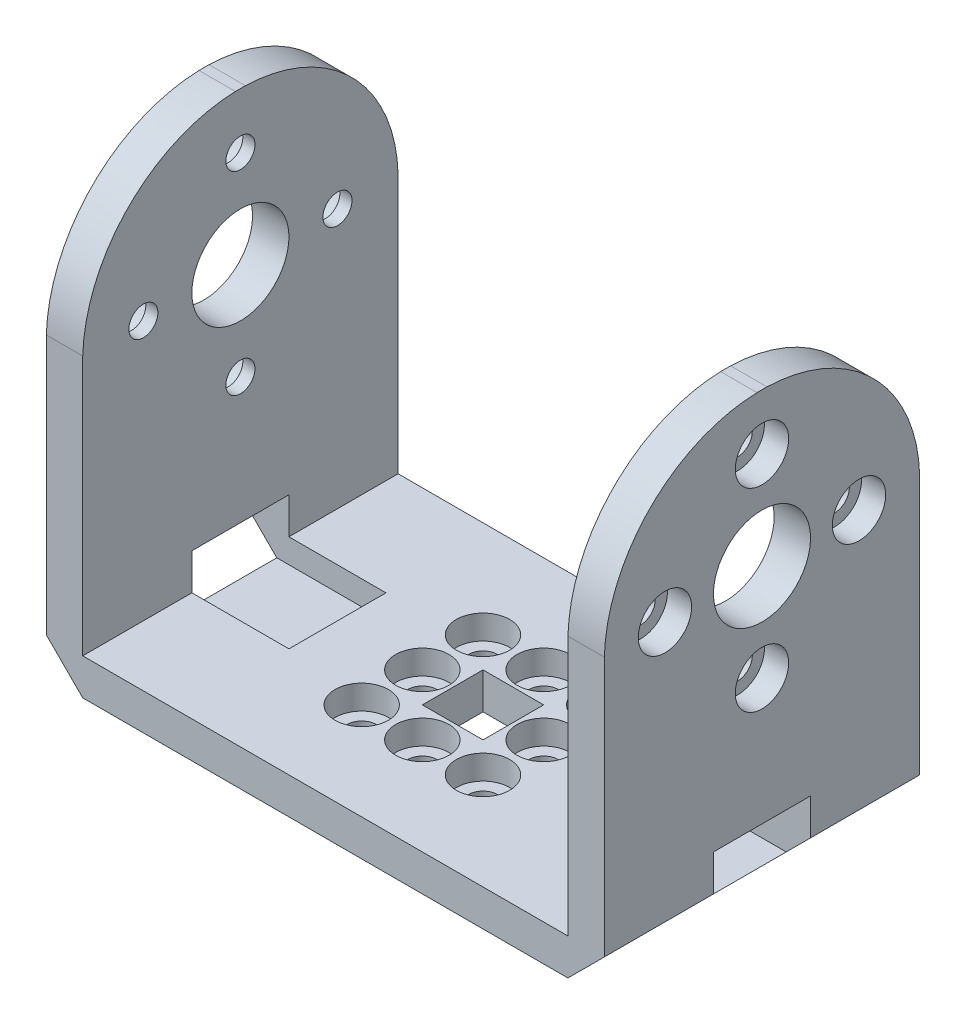
SolidWorks part; units mm, degrees
ref_plane "Front" through (0, 0, 0) normal (0, 0, 1) x (1, 0, 0)
ref_plane "Top" through (0, 0, 0) normal (0, 1, 0) x (1, 0, 0)
ref_plane "Right" through (0, 0, 0) normal (1, 0, 0) x (0, 0, -1)
sketch "草图1" plane through (0, 0, 0) normal (0, 1, 0) x (1, 0, 0)
  line L1 (-23, 13) -> (23, 13)
  line L2 (-23, 13) -> (-23, -13)
  line L3 (-23, -13) -> (23, -13)
  line L4 (23, 13) -> (23, -13)
  line L5 (-23, 13) -> (23, -13) construction
  line L6 (-23, -13) -> (23, 13) construction
  point P0 (0, 0)
  dimension "D1" = 46
  dimension "D2" = 26
extrude "凸台-拉伸1" add sketch "草图1" along normal blind 3
sketch "草图2" plane through (0, 3, 0) normal (0, 1, 0) x (1, 0, 0)
  line L0 (-23, -13) -> (23, -13) construction
  line L1 (-23, 13) -> (-20, 13)
  line L2 (-23, 13) -> (-23, -13)
  line L3 (-23, -13) -> (-20, -13)
  line L4 (-20, 13) -> (-20, -13)
  line L6 (23, 13) -> (20, 13)
  line L7 (23, 13) -> (23, -13)
  line L8 (23, -13) -> (20, -13)
  line L9 (20, 13) -> (20, -13)
extrude "凸台-拉伸2" add sketch "草图2" along normal blind 34
sketch "草图3" plane through (-23, 0, 0) normal (-1, 0, 0) x (0, 0, 1)
  line L0 (-13, 37) -> (-13, 0) construction
  line L1 (13, 37) -> (13, 0) construction
  arc A1 (-13, 23.5872) -> (13, 24.4128) centre (0, 24) cw
extrude "切除-拉伸1" cut sketch "草图3" against normal through all and the other way through all body kept at (-23, 0, -13)
sketch "草图4" plane through (-23, 0, 0) normal (-1, 0, 0) x (0, 0, 1)
  line L0 (-13, 24.4128) -> (13, 24.4128) construction
  line L1 (0, 37) -> (0, 0) construction
  line L2 (-0.4128, 37) -> (0.4128, 37) construction
  line L3 (-13, 0) -> (13, 0) construction
  circle A1 centre (0, 24.4128) radius 4
extrude "切除-拉伸2" cut sketch "草图4" against normal through all
sketch "草图7" plane through (-23, 0, 0) normal (-1, 0, 0) x (0, 0, 1)
  line L0 (-13, 24.4128) -> (13, 24.4128) construction
  line L1 (0, 37) -> (0, 10.3049) construction
  line L2 (-0.4128, 37) -> (0.4128, 37) construction
  point P4 (8, 24.4128)
  point P5 (0, 24.4128)
  point P11 (0, 32.4128)
  point P12 (-8, 24.4128)
  point P13 (0, 16.4128)
  dimension "D1" = 8
  dimension "D2" = 8
  dimension "D3" = 8
  dimension "D4" = 8
hole_wizard "M2 凹头盖螺钉的柱形沉头孔2" positions "3D草图2" profile "草图8" counterbore size "M2" standard "ANSI Metric" end condition up to next
sketch3d "3D草图2"
  point P0 (-23, 32.4128, 0)
  point P3 (-23, 24.4128, -8)
  point P6 (-23, 24.4128, 8)
  point P9 (-23, 16.4128, 0)
sketch "草图8" plane through (-23, 32.4128, 0) normal (0, 1, 0) x (0, 0, 1)
  line L0 (0, 0) -> (0, 46)
  line L1 (0, 46) -> (1.2, 46)
  line L3 (1.2, 46) -> (1.2, 2)
  line L4 (1.2, 2) -> (2.2, 2)
  line L5 (2.2, 2) -> (2.2, 0)
  line L7 (2.2, 0) -> (0, 0)
  line L11 (0, -6.35) -> (0, 107.95) construction
  dimension "通孔孔直径" = 2.4
  dimension "通孔孔深度" = 46
  dimension "柱形沉头孔直径" = 4.4
  dimension "柱形沉头孔深度" = 2
mirror "镜向2" about plane through (0, 0, 0) normal (1, 0, 0) of "M2 凹头盖螺钉的柱形沉头孔2"
chamfer "倒角1" distance 3 angle 45 2 edges at (23, 0, 0) (-23, 0, 0)
sketch "草图15" plane through (23, 0, 0) normal (1, 0, 0) x (0, 0, -1)
  line L0 (-13, 3) -> (13, 3) construction
  line L1 (4, 6) -> (-4, 6)
  line L2 (4, 6) -> (4, 1)
  line L3 (4, 1) -> (-4, 1)
  line L4 (-4, 6) -> (-4, 1)
  point P0 (0, 3)
  dimension "D1" = 8
  dimension "D2" = 5
extrude "切除-拉伸8" cut sketch "草图15" against normal blind 11
mirror "镜向3" about plane through (0, 0, 0) normal (1, 0, 0) of "切除-拉伸8"
sketch "草图18" plane through (0, 3, 0) normal (0, 1, 0) x (1, 0, 0)
  line L1 (-2.5, 2.5) -> (2.5, 2.5)
  line L2 (-2.5, 2.5) -> (-2.5, -2.5)
  line L3 (-2.5, -2.5) -> (2.5, -2.5)
  line L4 (2.5, 2.5) -> (2.5, -2.5)
  line L5 (-2.5, 2.5) -> (2.5, -2.5) construction
  line L6 (-2.5, -2.5) -> (2.5, 2.5) construction
  point P0 (0, 0)
  dimension "D1" = 5
  dimension "D2" = 5
extrude "切除-拉伸9" cut sketch "草图18" against normal through all both and the other way through all
sketch "草图19" plane through (0, 3, 0) normal (0, 1, 0) x (1, 0, 0)
  point P0 (-5, 5)
  point P4 (0, 5)
  point P5 (5, 5)
  point P6 (0, 0)
  point P7 (5, 0)
  point P8 (0, -5)
  point P9 (5, -5)
  point P10 (-5, 0)
  point P11 (-5, -5)
  dimension "D1" = 5
  dimension "D2" = 5
  dimension "D3" = 3
  dimension "D4" = 3
hole_wizard "M2 凹头盖螺钉的柱形沉头孔4" positions "3D草图4" profile "草图20" counterbore size "M2" standard "ANSI Metric" end condition through all
sketch3d "3D草图4"
  point P0 (-5, 3, -5)
  point P3 (-5, 3, 0)
  point P6 (-5, 3, 5)
  point P9 (0, 3, 5)
  point P12 (5, 3, 5)
  point P15 (5, 3, 0)
  point P18 (5, 3, -5)
  point P21 (0, 3, -5)
sketch "草图20" plane through (-5, 3, -5) normal (1, 0, 0) x (0, 0, 1)
  line L0 (0, 0) -> (0, 3)
  line L1 (0, 3) -> (1.2, 3)
  line L3 (1.2, 3) -> (1.2, 2)
  line L4 (1.2, 2) -> (2.2, 2)
  line L5 (2.2, 2) -> (2.2, 0)
  line L7 (2.2, 0) -> (0, 0)
  line L11 (0, -6.35) -> (0, 107.95) construction
  dimension "通孔孔直径" = 2.4
  dimension "通孔孔深度" = 3
  dimension "柱形沉头孔直径" = 4.4
  dimension "柱形沉头孔深度" = 2
